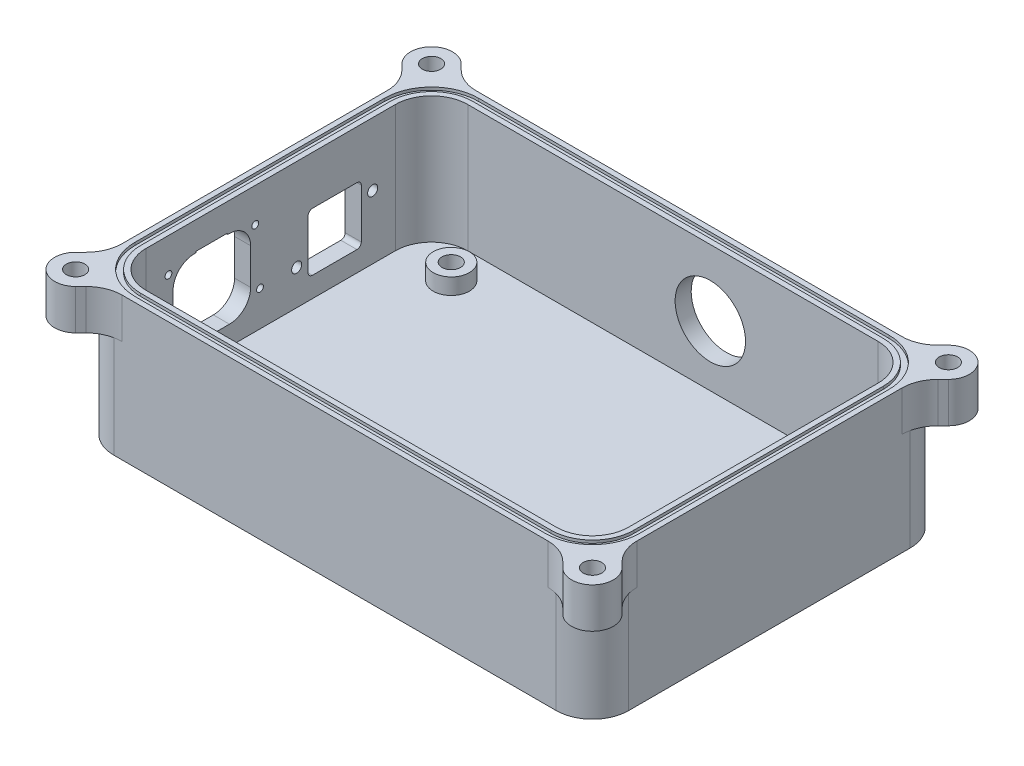
SolidWorks part; units mm, degrees
note: The reader was unsure of these and kept them because the rebuilt part matched: shared geometry of "Sketch7<4>".
ref_plane "Front Plane" through (0, 0, 0) normal (0, 0, 1) x (1, 0, 0)
ref_plane "Top Plane" through (0, 0, 0) normal (0, 1, 0) x (1, 0, 0)
ref_plane "Right Plane" through (0, 0, 0) normal (1, 0, 0) x (0, 0, -1)
sketch "Sketch1" plane through (0, 0, 0) normal (0, 1, 0) x (1, 0, 0)
  line L1 (76.2, 50.8) -> (-76.2, 50.8)
  line L2 (76.2, 50.8) -> (76.2, -50.8)
  line L3 (76.2, -50.8) -> (-76.2, -50.8)
  line L4 (-76.2, 50.8) -> (-76.2, -50.8)
  line L5 (76.2, 50.8) -> (-76.2, -50.8) construction
  line L6 (76.2, -50.8) -> (-76.2, 50.8) construction
  point P0 (0, 0)
  dimension "D1" = 152.4
  dimension "D2" = 101.6
extrude "Boss-Extrude1" add sketch "Sketch1" along normal blind 40.005 contours L4 L3 L2 L1
shell "Shell1" thickness 5.08
sketch "Sketch3" plane through (-81.28, 0, 0) normal (1, 0, 0) x (0, 0, -1)
  line L40 (13.196, 24.7028) -> (27.236, 24.7028)
  line L41 (11.816, 23.3228) -> (11.816, 7.7828)
  line L42 (13.196, 6.4028) -> (27.236, 6.4028)
  line L43 (28.616, 23.3228) -> (28.616, 7.7828)
  line L44 (11.816, 24.7028) -> (28.616, 6.4028) construction
  line L45 (11.816, 6.4028) -> (28.616, 24.7028) construction
  line L46 (-24.11, 30.9225) -> (-13.01, 30.9225)
  line L47 (-30.81, 24.2225) -> (-30.81, 12.8225)
  line L48 (-24.11, 6.1225) -> (-13.01, 6.1225)
  line L49 (-6.31, 24.2225) -> (-6.31, 12.8225)
  line L50 (-30.81, 30.9225) -> (-6.31, 6.1225) construction
  line L51 (-30.81, 6.1225) -> (-6.31, 30.9225) construction
  line L61 (8.216, 13.5528) -> (8.216, 8.5528) construction
  line L62 (-2.275, 11.1225) -> (-4.445, 11.1225) construction
  line L63 (-13.56, 30.9225) -> (-13.56, 31.3225)
  line L64 (-13.56, 31.3225) -> (-23.56, 31.3225)
  line L65 (-23.56, 31.3225) -> (-23.56, 30.9225)
  circle A2 centre (8.216, 11.0528) radius 1.6
  circle A3 centre (32.216, 20.0528) radius 1.6
  arc A4 (11.816, 7.7828) -> (13.196, 6.4028) centre (13.196, 7.7828) ccw
  arc A5 (27.236, 6.4028) -> (28.616, 7.7828) centre (27.236, 7.7828) ccw
  arc A6 (27.236, 24.7028) -> (28.616, 23.3228) centre (27.236, 23.3228) cw
  arc A7 (13.196, 24.7028) -> (11.816, 23.3228) centre (13.196, 23.3228) ccw
  arc A8 (-30.81, 12.8225) -> (-24.11, 6.1225) centre (-24.11, 12.8225) ccw
  arc A9 (-13.01, 6.1225) -> (-6.31, 12.8225) centre (-13.01, 12.8225) ccw
  arc A10 (-13.01, 30.9225) -> (-6.31, 24.2225) centre (-13.01, 24.2225) cw
  arc A11 (-24.11, 30.9225) -> (-30.81, 24.2225) centre (-24.11, 24.2225) ccw
  spline S34 degree 3 poles (32.216, 22.5528) (27.216, 22.5528) (27.216, 17.5528) (32.216, 17.5528) knots 0 0 0 0 1 1 1 1 weights 1 0.333333 0.333333 1 construction
  spline S35 degree 3 poles (32.216, 17.5528) (37.216, 17.5528) (37.216, 22.5528) (32.216, 22.5528) knots 0 0 0 0 1 1 1 1 weights 1 0.333333 0.333333 1 construction
  spline S36 degree 3 poles (8.216, 8.5528) (13.216, 8.5528) (13.216, 13.5528) (8.216, 13.5528) knots 0 0 0 0 1 1 1 1 weights 1 0.333333 0.333333 1 construction
  spline S37 degree 3 poles (8.216, 13.5528) (3.216, 13.5528) (3.216, 8.5528) (8.216, 8.5528) knots 0 0 0 0 1 1 1 1 weights 1 0.333333 0.333333 1 construction
  spline S38 degree 3 poles (32.216, 22.5528) (27.216, 22.5528) (27.216, 17.5528) (32.216, 17.5528) knots 0 0 0 0 1 1 1 1 weights 1 0.333333 0.333333 1 construction
  spline S39 degree 3 poles (32.216, 17.5528) (37.216, 17.5528) (37.216, 22.5528) (32.216, 22.5528) knots 0 0 0 0 1 1 1 1 weights 1 0.333333 0.333333 1 construction
  spline S40 degree 3 poles (8.216, 8.5528) (13.216, 8.5528) (13.216, 13.5528) (8.216, 13.5528) knots 0 0 0 0 1 1 1 1 weights 1 0.333333 0.333333 1 construction
  spline S41 degree 3 poles (8.216, 13.5528) (3.216, 13.5528) (3.216, 8.5528) (8.216, 8.5528) knots 0 0 0 0 1 1 1 1 weights 1 0.333333 0.333333 1 construction
  spline S43 degree 3 poles (30.8305, 20.8531) (31.1234, 21.3601) (31.6305, 21.6528) (32.216, 21.6528) knots 0 0 0 0 1 1 1 1 weights 1 0.91072 0.91072 1 construction
  spline S44 degree 3 poles (32.216, 21.6528) (35.416, 21.6528) (35.416, 18.4528) (32.216, 18.4528) knots 0 0 0 0 1 1 1 1 weights 1 0.333333 0.333333 1 construction
  spline S45 degree 3 poles (32.216, 18.4528) (31.6304, 18.4528) (31.1232, 18.7456) (30.8304, 19.2528) knots 0 0 0 0 1 1 1 1 weights 1 0.910684 0.910684 1 construction
  spline S50 degree 3 poles (-34.845, 11.1225) (-34.845, 13.2925) (-32.675, 13.2925) (-32.675, 11.1225) knots 0 0 0 0 1 1 1 1 weights 1 0.333333 0.333333 1 construction
  spline S51 degree 3 poles (-32.675, 11.1225) (-32.675, 8.9525) (-34.845, 8.9525) (-34.845, 11.1225) knots 0 0 0 0 1 1 1 1 weights 1 0.333333 0.333333 1 construction
  spline S52 degree 3 poles (-33.345, 29.2225) (-33.345, 31.3925) (-31.175, 31.3925) (-31.175, 29.2225) knots 0 0 0 0 1 1 1 1 weights 1 0.333333 0.333333 1 construction
  spline S53 degree 3 poles (-31.175, 29.2225) (-31.175, 27.0525) (-33.345, 27.0525) (-33.345, 29.2225) knots 0 0 0 0 1 1 1 1 weights 1 0.333333 0.333333 1 construction
  spline S54 degree 3 poles (-5.945, 29.2225) (-5.945, 31.3925) (-3.775, 31.3925) (-3.775, 29.2225) knots 0 0 0 0 1 1 1 1 weights 1 0.333333 0.333333 1 construction
  spline S55 degree 3 poles (-3.775, 29.2225) (-3.775, 27.0525) (-5.945, 27.0525) (-5.945, 29.2225) knots 0 0 0 0 1 1 1 1 weights 1 0.333333 0.333333 1 construction
  spline S56 degree 3 poles (-4.445, 11.1225) (-4.445, 13.2925) (-2.275, 13.2925) (-2.275, 11.1225) knots 0 0 0 0 1 1 1 1 weights 1 0.333333 0.333333 1 construction
  spline S57 degree 3 poles (-2.275, 11.1225) (-2.275, 8.9525) (-4.445, 8.9525) (-4.445, 11.1225) knots 0 0 0 0 1 1 1 1 weights 1 0.333333 0.333333 1 construction
  spline S59 degree 3 poles (30.8305, 20.8531) (31.1234, 21.3601) (31.6305, 21.6528) (32.216, 21.6528) knots 0 0 0 0 1 1 1 1 weights 1 0.91072 0.91072 1
  spline S60 degree 3 poles (32.216, 21.6528) (35.416, 21.6528) (35.416, 18.4528) (32.216, 18.4528) knots 0 0 0 0 1 1 1 1 weights 1 0.333333 0.333333 1
  spline S61 degree 3 poles (32.216, 18.4528) (31.6304, 18.4528) (31.1232, 18.7456) (30.8304, 19.2528) knots 0 0 0 0 1 1 1 1 weights 1 0.910684 0.910684 1
  spline S66 degree 3 poles (-34.845, 11.1225) (-34.845, 13.2925) (-32.675, 13.2925) (-32.675, 11.1225) knots 0 0 0 0 1 1 1 1 weights 1 0.333333 0.333333 1
  spline S67 degree 3 poles (-32.675, 11.1225) (-32.675, 8.9525) (-34.845, 8.9525) (-34.845, 11.1225) knots 0 0 0 0 1 1 1 1 weights 1 0.333333 0.333333 1
  spline S68 degree 3 poles (-33.345, 29.2225) (-33.345, 31.3925) (-31.175, 31.3925) (-31.175, 29.2225) knots 0 0 0 0 1 1 1 1 weights 1 0.333333 0.333333 1
  spline S69 degree 3 poles (-31.175, 29.2225) (-31.175, 27.0525) (-33.345, 27.0525) (-33.345, 29.2225) knots 0 0 0 0 1 1 1 1 weights 1 0.333333 0.333333 1
  spline S70 degree 3 poles (-5.945, 29.2225) (-5.945, 31.3925) (-3.775, 31.3925) (-3.775, 29.2225) knots 0 0 0 0 1 1 1 1 weights 1 0.333333 0.333333 1
  spline S71 degree 3 poles (-3.775, 29.2225) (-3.775, 27.0525) (-5.945, 27.0525) (-5.945, 29.2225) knots 0 0 0 0 1 1 1 1 weights 1 0.333333 0.333333 1
  spline S72 degree 3 poles (-4.445, 11.1225) (-4.445, 13.2925) (-2.275, 13.2925) (-2.275, 11.1225) knots 0 0 0 0 1 1 1 1 weights 1 0.333333 0.333333 1
  spline S73 degree 3 poles (-2.275, 11.1225) (-2.275, 8.9525) (-4.445, 8.9525) (-4.445, 11.1225) knots 0 0 0 0 1 1 1 1 weights 1 0.333333 0.333333 1
  point P0 (32.216, 20.0528)
  point P1 (-3.36, 11.1225)
  point P6 (20.216, 15.5528)
  point P20 (-18.56, 18.5225)
  point P38 (8.216, 11.0528)
  dimension "D1" = 3.2
  dimension "D6" = 18.3
  dimension "D10" = 1.38
  dimension "D15" = 6.7
  dimension "D2" = 4.5
  dimension "D3" = 2.95
  dimension "D4" = 24
  dimension "D5" = 9
  dimension "D7" = 16.8
  dimension "D8" = 5
  dimension "D9" = 12
  dimension "D11" = 24.5
  dimension "D12" = 10
  dimension "D13" = 24.8
  dimension "D14" = 25.2
  dimension "D16" = 5
sketch "Sketch5" plane through (0, 0, 0) normal (0, -1, 0) x (-1, 0, 0)
  circle A0 centre (59.182, -40.005) radius 2.1 construction
  circle A1 centre (-15.748, -24.765) radius 2.1 construction
  circle A2 centre (-51.308, 40.005) radius 2.1 construction
  circle A3 centre (59.182, 40.005) radius 2.1 construction
  circle A4 centre (59.182, -40.005) radius 2.1 construction
  circle A5 centre (-15.748, -24.765) radius 2.1 construction
  circle A6 centre (-51.308, 40.005) radius 2.1 construction
  circle A7 centre (59.182, 40.005) radius 2.1 construction
  circle A8 centre (59.182, 40.005) radius 2.921
  circle A9 centre (59.182, -40.005) radius 2.921
  circle A10 centre (-15.748, -24.765) radius 2.921
  circle A11 centre (-51.308, 40.005) radius 2.921
  circle A12 centre (59.182, 40.005) radius 5.715
  circle A13 centre (-51.308, 40.005) radius 5.715
  circle A14 centre (-15.748, -24.765) radius 5.715
  circle A15 centre (59.182, -40.005) radius 5.715
  dimension "D1" = 5.842
  dimension "D2" = 11.43
extrude "Boss-Extrude2" add sketch "Sketch5" against normal blind 5.08
extrude "Cut-Extrude2" cut sketch "Sketch3" along normal up to surface (5.08 mm away) contours A7 L40 A6 L43 A5 L42 A4 L41 | A3 | A2 | A11 L46 A10 L49 A9 L48 A8 L47 | S70 S71 | S72 S73 | S68 S69 | S66 S67 | L65 L64 L63 L46 up to face at (-76.2, 20.0025, 0)
sketch "Sketch7" plane through (0, 40.005, 0) normal (0, 1, 0) x (1, 0, 0)
  line L0 (-86.2634, 51.5129) -> (-76.2, 41.4495)
  line L2 (-76.2, 50.8) -> (-76.2, -50.8) construction
  line L4 (-81.28, 55.88) -> (-76.2, 50.8)
  line L5 (-76.2, 50.8) -> (-86.9763, 61.5763)
  line L6 (-76.9129, 60.8634) -> (-86.2634, 51.5129) construction
  line L7 (-76.9129, 60.8634) -> (-66.8495, 50.8)
  line L8 (76.2, 50.8) -> (-76.2, 50.8) construction
  line L18 (-76.2, 41.4495) -> (-76.2, 50.8)
  line L19 (-76.2, 50.8) -> (-66.8495, 50.8)
  circle A1 centre (-81.5882, 56.1882) radius 2.921
  arc A8 (-76.9129, 60.8634) -> (-86.2634, 51.5129) centre (-81.5882, 56.1882) ccw
  point P1 (-76.2, 50.637)
  point P16 (0, 0)
  point P42 (-76.0367, 50.8)
  point P43 (-86.6682, 61.2682)
  point P44 (-82.6112, 57.2112)
  line M51 (81.28, 55.88) -> (-81.28, 55.88)
  line M56 (-81.28, 55.88) -> (-81.28, -55.88)
  dimension "D1" = 7.62
  dimension "D2" = 5.842
  dimension "D3" = 6.6118
extrude "Boss-Extrude3" add sketch "Sketch7" against normal blind 12.7 contours L19 L7 A8 L0 L18
extrude "Cut-Extrude3" cut sketch "Sketch7<4>" against normal blind 8.89 contours L6 L5 A1 | L5 L6 A1 M56 | A1 L6 L5 M51 | L4 A1 M51 | A1 L4 M56 | L6 A1 L5
sketch "Sketch7<4>" plane through (0, 40.005, 0) normal (0, 1, 0) x (1, 0, 0) same geometry as "Sketch7"
mirror "Mirror1" about plane through (0, 0, 0) normal (1, 0, 0) of "Cut-Extrude3", "Boss-Extrude3" second plane through (0, 0, 0) second plane normal (0, 0, 1)
fillet "Fillet1" radius 11.43 8 edges at (-81.28, 11.1125, -55.88) (-81.28, 11.1125, 55.88) (81.28, 11.1125, 55.88) (81.28, 11.1125, -55.88) (76.2, 20.0025, 50.8) (76.2, 20.0025, -50.8) (-76.2, 20.0025, -50.8) (-76.2, 20.0025, 50.8)
fillet "Fillet2" radius 11.43 16 edges at (70.8122, 40.005, -55.8394) (81.2394, 40.005, -45.4122) (81.2394, 40.005, 45.4122) (70.8122, 40.005, 55.8394) (-70.8122, 40.005, 55.8394) (-81.2394, 40.005, 45.4122) (-81.2394, 40.005, -45.4122) (-70.8122, 40.005, -55.8394) (-71.7675, 33.655, -55.718) (-81.118, 33.655, -46.3675) (-81.118, 33.655, 46.3675) (-71.7675, 33.655, 55.718) (71.7675, 33.655, 55.718) (81.118, 33.655, 46.3675) (81.118, 33.655, -46.3675) (71.7675, 33.655, -55.718)
sketch "Sketch8" plane through (0, 40.005, 0) normal (0, 1, 0) x (1, 0, 0)
  line L29 (-79.629, 39.37) -> (-79.629, -39.37)
  line L30 (-64.77, -54.229) -> (64.77, -54.229)
  line L31 (79.629, -39.37) -> (79.629, 39.37)
  line L32 (64.77, 54.229) -> (-64.77, 54.229)
  line L33 (-78.74, 39.37) -> (-78.74, -39.37)
  line L34 (-64.77, -53.34) -> (64.77, -53.34)
  line L35 (78.74, -39.37) -> (78.74, 39.37)
  line L36 (64.77, 53.34) -> (-64.77, 53.34)
  line L37 (-78.74, 39.37) -> (-78.74, -39.37) construction
  line L38 (-64.77, -53.34) -> (64.77, -53.34) construction
  line L39 (78.74, -39.37) -> (78.74, 39.37) construction
  line L40 (64.77, 53.34) -> (-64.77, 53.34) construction
  line L41 (-77.851, 39.37) -> (-77.851, -39.37)
  line L42 (-64.77, -52.451) -> (64.77, -52.451)
  line L43 (77.851, -39.37) -> (77.851, 39.37)
  line L44 (64.77, 52.451) -> (-64.77, 52.451)
  arc A35 (-64.77, 54.229) -> (-79.629, 39.37) centre (-64.77, 39.37) ccw
  arc A36 (-79.629, -39.37) -> (-64.77, -54.229) centre (-64.77, -39.37) ccw
  arc A37 (64.77, -54.229) -> (79.629, -39.37) centre (64.77, -39.37) ccw
  arc A38 (79.629, 39.37) -> (64.77, 54.229) centre (64.77, 39.37) ccw
  arc A39 (-78.74, -39.37) -> (-64.77, -53.34) centre (-64.77, -39.37) ccw
  arc A40 (64.77, -53.34) -> (78.74, -39.37) centre (64.77, -39.37) ccw
  arc A41 (78.74, 39.37) -> (64.77, 53.34) centre (64.77, 39.37) ccw
  arc A42 (-64.77, 53.34) -> (-78.74, 39.37) centre (-64.77, 39.37) ccw
  arc A43 (-78.74, -39.37) -> (-64.77, -53.34) centre (-64.77, -39.37) ccw construction
  arc A44 (64.77, -53.34) -> (78.74, -39.37) centre (64.77, -39.37) ccw construction
  arc A45 (78.74, 39.37) -> (64.77, 53.34) centre (64.77, 39.37) ccw construction
  arc A46 (-64.77, 53.34) -> (-78.74, 39.37) centre (-64.77, 39.37) ccw construction
  arc A47 (-64.77, 52.451) -> (-77.851, 39.37) centre (-64.77, 39.37) ccw
  arc A48 (-77.851, -39.37) -> (-64.77, -52.451) centre (-64.77, -39.37) ccw
  arc A49 (64.77, -52.451) -> (77.851, -39.37) centre (64.77, -39.37) ccw
  arc A50 (77.851, 39.37) -> (64.77, 52.451) centre (64.77, 39.37) ccw
  dimension "D2" = 0.889
  dimension "D1" = 2.54
  dimension "D3" = 0.889
extrude "Cut-Extrude4" cut sketch "Sketch8" against normal blind 0.889
sketch "Sketch10" plane through (0, 0, -55.88) normal (0, 0, -1) x (-1, 0, 0)
  line L0 (-69.85, -5.08) -> (69.85, -5.08) construction
  circle A0 centre (-11.8057, 19.05) radius 11.1125
  point P2 (-19.2822, 15.9767)
  point P5 (0, 0)
  point P6 (-11.8057, 19.05)
  dimension "D1" = 22.225
  dimension "D2" = 24.13
extrude "Cut-Extrude5" cut sketch "Sketch10" against normal up to surface (5.08 mm away) up to face at (0, 20.0025, -50.8)
